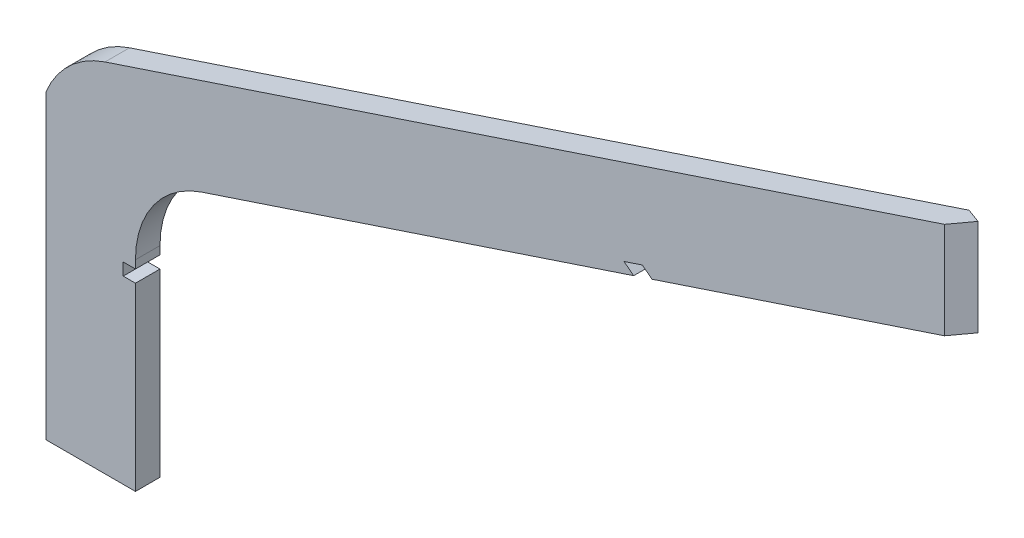
SolidWorks part; units mm, degrees
material "6061 Alloy"
ref_plane "Front Plane" through (0, 0, 0) normal (0, 0, 1) x (1, 0, 0)
ref_plane "Top Plane" through (0, 0, 0) normal (0, 1, 0) x (1, 0, 0)
ref_plane "Right Plane" through (0, 0, 0) normal (1, 0, 0) x (0, 0, -1)
sketch "Sketch1" plane through (0, 0, 0) normal (0, 0, 1) x (1, 0, 0)
  line L13 (-95.4803, -80.7064) -> (-95.4803, -131.0852)
  line L16 (-120.4803, -131.0852) -> (119.5197, -131.0852)
  line L17 (119.5197, 8.8096) -> (119.5197, 33.8096)
  line L18 (-78.3677, -56.9832) -> (119.5197, 8.8096)
  line L20 (119.5197, 8.8096) -> (119.5197, -131.0852)
  line L21 (119.5197, 33.8096) -> (-103.3677, -40.2951)
  line L22 (-120.4803, -64.0183) -> (-120.4803, -131.0852)
  line L23 (-120.4803, -131.0852) -> (-120.4803, -132.6727)
  line L24 (-120.4803, -132.6727) -> (-95.4803, -132.6727)
  line L25 (-95.4803, -132.6727) -> (-95.4803, -131.0852)
  arc A0 (-95.4803, -80.7064) -> (-78.3677, -56.9832) centre (-70.4803, -80.7064) cw
  arc A1 (-120.4803, -64.0183) -> (-103.3677, -40.2951) centre (-95.4803, -64.0183) cw
  dimension "D5" = 25
  dimension "D1" = 25
  dimension "D2" = 240
  dimension "D3" = 139.8948
  dimension "D4" = 25
extrude "Boss-Extrude1" add sketch "Sketch1" along normal blind 3.175 and the other way blind 3.175 contours L17 L21 A1 L22 L23 L24 L25 L13 A0 L18
sketch "Sketch2" plane through (0, -132.6727, 0) normal (0, -1, 0) x (1, 0, 0)
  line L10 (-120.4803, 0) -> (-120.4803, 3.175)
  line L12 (-120.4803, 3.175) -> (-118.6472, 3.175)
  line L14 (-120.4803, 0) -> (-118.6472, 3.175)
extrude "Cut-Extrude3" cut sketch "Sketch2" against normal through all
mirror "Mirror3" about plane through (0, 0, 0) normal (0, 0, 1) of "Cut-Extrude3"
sketch "Sketch3" plane through (0, -132.6727, 0) normal (0, -1, 0) x (1, 0, 0)
  line L1 (119.5197, 3.175) -> (114.0204, 3.175)
  line L5 (119.5197, 3.175) -> (119.5197, 0)
  line L6 (119.5197, -3.175) -> (119.5197, 3.175) construction
  line L7 (119.5197, 0) -> (114.0204, 3.175)
extrude "Cut-Extrude5" cut sketch "Sketch3" against normal through all
mirror "Mirror4" about plane through (0, 0, 0) normal (0, 0, 1) of "Cut-Extrude5"
sketch "Sketch6" plane through (0, 0, 3.175) normal (0, 0, 1) x (1, 0, 0)
  line L0 (33.5465, -19.7744) -> (38.2911, -18.197)
  line L8 (33.5465, -19.7744) -> (31.0251, -17.8449)
  line L9 (31.0251, -17.8449) -> (35.7697, -16.2674)
  line L11 (35.7697, -16.2674) -> (38.2911, -18.197)
extrude "Cut-Extrude6" cut sketch "Sketch6" against normal up to surface (6.35 mm away) contours L9 L11 L0 L8 up to face at (-48.4192, -56.8185, -3.175)
sketch "Sketch8" plane through (0, 0, 3.175) normal (0, 0, 1) x (1, 0, 0)
  line L1 (-95.4803, -132.6727) -> (-95.4803, -80.7064) construction
  line L6 (-95.4803, -85.9665) -> (-98.6553, -85.9665)
  line L7 (-98.6553, -85.9665) -> (-98.6553, -82.7915)
  line L8 (-98.6553, -82.7915) -> (-95.4803, -82.7915)
  line L9 (-95.4803, -82.7915) -> (-95.4803, -85.9665)
extrude "Cut-Extrude7" cut sketch "Sketch8" against normal up to surface (6.35 mm away) up to face at (-20.7268, -43.886, -3.175)
sketch "Sketch9" plane through (0, 0, 3.175) normal (0, 0, 1) x (1, 0, 0)
  line L0 (-120.4803, -64.0183) -> (-120.4803, -132.6727) construction
  line L1 (-120.4803, -132.6727) -> (-118.6472, -132.6727) construction
  line L2 (-95.4803, -132.6727) -> (-95.4803, -85.9665) construction
  line L3 (-95.4803, -85.9665) -> (-98.6553, -85.9665) construction
  line L4 (-98.6553, -85.9665) -> (-98.6553, -82.7915) construction
  line L5 (-98.6553, -82.7915) -> (-95.4803, -82.7915) construction
  line L6 (-95.4803, -82.7915) -> (-95.4803, -80.7064) construction
  line L7 (-78.3677, -56.9832) -> (33.5465, -19.7744) construction
  line L8 (33.5465, -19.7744) -> (31.0251, -17.8449) construction
  line L9 (31.0251, -17.8449) -> (35.7697, -16.2674) construction
  line L10 (35.7697, -16.2674) -> (38.2911, -18.197) construction
  line L11 (38.2911, -18.197) -> (114.0204, 6.9812) construction
  line L13 (114.0204, 31.9812) -> (-103.3677, -40.2951) construction
  line L14 (-118.6472, -132.6727) -> (-95.4803, -132.6727) construction
  line L15 (-120.4803, -64.0183) -> (-120.4803, -132.6727)
  line L16 (-120.4803, -132.6727) -> (-118.6472, -132.6727)
  line L17 (-95.4803, -132.6727) -> (-95.4803, -85.9665)
  line L18 (-95.4803, -85.9665) -> (-98.6553, -85.9665)
  line L19 (-98.6553, -85.9665) -> (-98.6553, -82.7915)
  line L20 (-98.6553, -82.7915) -> (-95.4803, -82.7915)
  line L21 (-95.4803, -82.7915) -> (-95.4803, -80.7064)
  line L22 (-78.3677, -56.9832) -> (33.5465, -19.7744)
  line L23 (33.5465, -19.7744) -> (31.0251, -17.8449)
  line L24 (31.0251, -17.8449) -> (35.7697, -16.2674)
  line L25 (35.7697, -16.2674) -> (38.2911, -18.197)
  line L26 (38.2911, -18.197) -> (114.0204, 6.9812)
  line L28 (114.0204, 31.9812) -> (-103.3677, -40.2951)
  line L29 (-118.6472, -132.6727) -> (-95.4803, -132.6727)
  line L34 (114.0204, 6.9812) -> (119.5197, 8.8096)
  line L35 (119.5197, 8.8096) -> (119.5197, 33.8096)
  line L36 (119.5197, 33.8096) -> (114.0204, 31.9812)
  line L37 (114.0204, 31.9812) -> (114.0204, 6.9812)
  line L38 (114.0204, 6.9812) -> (119.5197, 8.8096)
  line L39 (119.5197, 8.8096) -> (119.5197, 33.8096)
  line L40 (119.5197, 33.8096) -> (114.0204, 31.9812)
  arc A0 (-118.6472, -54.6218) -> (-120.4803, -64.0183) centre (-95.4803, -64.0183) ccw construction
  arc A1 (-78.3677, -56.9832) -> (-95.4803, -80.7064) centre (-70.4803, -80.7064) ccw construction
  arc A2 (-103.3677, -40.2951) -> (-118.6472, -54.6218) centre (-95.4803, -64.0183) ccw construction
  arc A3 (-118.6472, -54.6218) -> (-120.4803, -64.0183) centre (-95.4803, -64.0183) ccw
  arc A4 (-78.3677, -56.9832) -> (-95.4803, -80.7064) centre (-70.4803, -80.7064) ccw
  arc A5 (-103.3677, -40.2951) -> (-118.6472, -54.6218) centre (-95.4803, -64.0183) ccw
  dimension "D1" = 0
